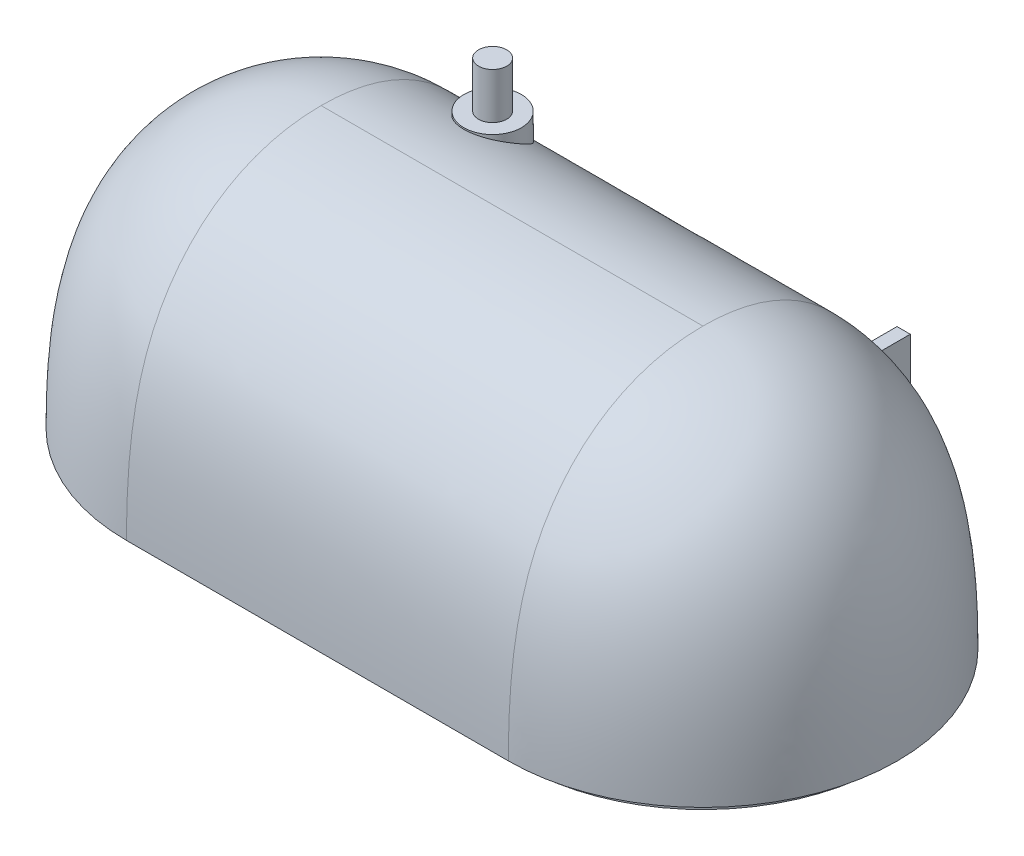
SolidWorks part; units mm, degrees
ref_plane "Front Plane" through (0, 0, 0) normal (0, 0, 1) x (1, 0, 0)
ref_plane "Top Plane" through (0, 0, 0) normal (0, 1, 0) x (1, 0, 0)
ref_plane "Right Plane" through (0, 0, 0) normal (1, 0, 0) x (0, 0, -1)
sketch "Sketch1" plane through (0, 0, 0) normal (0, 1, 0) x (1, 0, 0)
  line L0 (-41.915, 0) -> (41.915, 0) construction
  line L1 (-20.745, -21.17) -> (20.745, -21.17)
  line L2 (-20.745, -21.17) -> (-20.745, 21.17) construction
  line L3 (-20.745, 21.17) -> (20.745, 21.17)
  line L4 (20.745, -21.17) -> (20.745, 21.17) construction
  line L5 (-20.745, -21.17) -> (20.745, 21.17) construction
  line L6 (-20.745, 21.17) -> (20.745, -21.17) construction
  arc A0 (-20.745, -21.17) -> (-20.745, 21.17) centre (-20.745, 0) cw
  arc A1 (20.745, 21.17) -> (20.745, -21.17) centre (20.745, 0) cw
  point P0 (0, 0)
  dimension "D1" = 83.83
  dimension "D2" = 42.34
sketch "Sketch2" plane through (0, 0, 0) normal (1, 0, 0) x (0, 0, -1)
  line L0 (21.17, 0) -> (-21.17, 0) construction
  line L1 (21.17, 0) -> (-21.17, 0) construction
  line L2 (0, 0) -> (0, 31.55) construction
  line L3 (19.735, 0) -> (19.735, 1.19)
  line L4 (19.735, 1.19) -> (21.135, 1.19)
  line L5 (-19.735, 0) -> (19.735, 0)
  line L6 (-19.735, 1.19) -> (-21.135, 1.19)
  line L7 (-19.735, 0) -> (-19.735, 1.19)
  line L8 (18.1, 19.85) -> (18.1, 0) construction
  line L9 (18.1, 19.85) -> (-18.1, 19.85) construction
  line L10 (21.135, 1.19) -> (21.135, 0.6886) construction
  spline S0 degree 3 poles (21.135, 1.19) (21.135, 7.0764) (20.4011, 21.9995) (8.9089, 31.55) (0, 31.55) knots 0 0 0 0 0.467286 1 1 1 1
  spline S1 degree 3 poles (-21.135, 1.19) (-21.135, 7.0764) (-20.4011, 21.9995) (-8.9089, 31.55) (0, 31.55) knots 0 0 0 0 0.467286 1 1 1 1
  point P8 (0, 19.85)
  dimension "D1" = 31.55
  dimension "D2" = 39.47
  dimension "D3" = 1.19
  dimension "D4" = 1.4
  dimension "D5" = 36.2
  dimension "D6" = 19.85
extrude "Boss-Extrude2" add sketch "Sketch2" along normal up to vertex and the other way up to vertex up to point (20.745, 0, 21.17) other way up to point (-20.745, 0, 21.17)
sketch "Sketch4" plane through (-20.745, 0, 0) normal (-1, 0, 0) x (0, 0, 1)
  line L0 (0, 31.55) -> (0, 0)
  line L5 (-19.735, 1.19) -> (-19.735, 0)
  line L6 (-21.135, 1.19) -> (-19.735, 1.19)
  line L7 (19.735, 1.19) -> (21.135, 1.19)
  line L8 (19.735, 0) -> (19.735, 1.19)
  line L9 (-19.735, 0) -> (19.735, 0)
  line L12 (19.735, 1.19) -> (21.135, 1.19)
  line L13 (19.735, 0) -> (19.735, 1.19)
  line L14 (0, 0) -> (19.735, 0)
  spline S2 degree 3 poles (333.5549, -911.1802) (140.1511, 42.8638) (-153.2404, 81.7088) (86.9036, -145.8898) (-639.1994, 787.2913) knots -2.804305 -2.804305 -2.804305 -2.804305 0.532714 4.237911 4.237911 4.237911 4.237911 only from (0, 31.55) to (-21.135, 1.19)
  spline S3 degree 3 poles (2506.664, 3134.8984) (-251.1944, -284.8739) (340.5877, 177.8042) (-353.3586, -1.6005) (-731.6989, -3883.5105) knots -5.099916 -5.099916 -5.099916 -5.099916 0.467286 5.832152 5.832152 5.832152 5.832152 only from (21.135, 1.19) to (0, 31.55)
  spline S5 degree 3 poles (21.135, 1.19) (21.135, 7.0764) (20.4011, 21.9995) (8.9089, 31.55) (0, 31.55) knots 0 0 0 0 0.467286 1 1 1 1
  dimension "D1" = 0
revolve "Revolve2" add sketch "Sketch4" angle 180 about L0
mirror "Mirror2" about plane through (0, 0, 0) normal (1, 0, 0) of "Revolve2"
ref_plane "Plane1" through (0, 5.16, 0) normal (0, 1, 0) x (1, 0, 0)
sketch "Sketch5" plane through (0, 5.16, 0) normal (0, 1, 0) x (1, 0, 0)
  line L0 (20.745, 21.135) -> (-20.745, 21.135) construction
  line L1 (-21.34, 16.935) -> (-19.9, 16.935)
  line L2 (-21.34, 16.935) -> (-21.34, 21.935)
  line L3 (-21.34, 21.935) -> (-19.9, 21.935)
  line L4 (-19.9, 16.935) -> (-19.9, 21.935)
  line L5 (0, 0) -> (0, 16.9405) construction
  line L6 (19.9, 16.935) -> (19.9, 21.935)
  line L7 (21.34, 21.935) -> (19.9, 21.935)
  line L8 (21.34, 16.935) -> (21.34, 21.935)
  line L9 (21.34, 16.935) -> (19.9, 16.935)
  dimension "D1" = 5
  dimension "D2" = 0.8
  dimension "D3" = 1.44
  dimension "D4" = 39.8
extrude "Boss-Extrude3" add sketch "Sketch5" along normal blind 14.95
sketch "Sketch7" plane through (0, 5.16, 0) normal (0, 1, 0) x (1, 0, 0)
  line L0 (-14.9, 9.67) -> (-19.9, 9.67) construction
  line L1 (-19.9, 9.67) -> (-19.9, 17.9774) construction
  line L2 (-11.775, 12.795) -> (-11.775, 21.135) construction
  line L3 (20.745, 21.135) -> (-20.745, 21.135) construction
  circle A0 centre (-11.775, 9.67) radius 3.125
  dimension "D1" = 6.25
  dimension "D2" = 5
  dimension "D3" = 8.34
extrude "Boss-Extrude4" add sketch "Sketch7" along normal offset from surface (25.52 mm away) 30.68 up to plane "Top Plane"
sketch "Sketch8" plane through (0, 30.68, 0) normal (0, 1, 0) x (1, 0, 0)
  circle A0 centre (-11.775, 9.67) radius 1.535
  dimension "D1" = 3.07
extrude "Boss-Extrude5" add sketch "Sketch8" along normal blind 5
